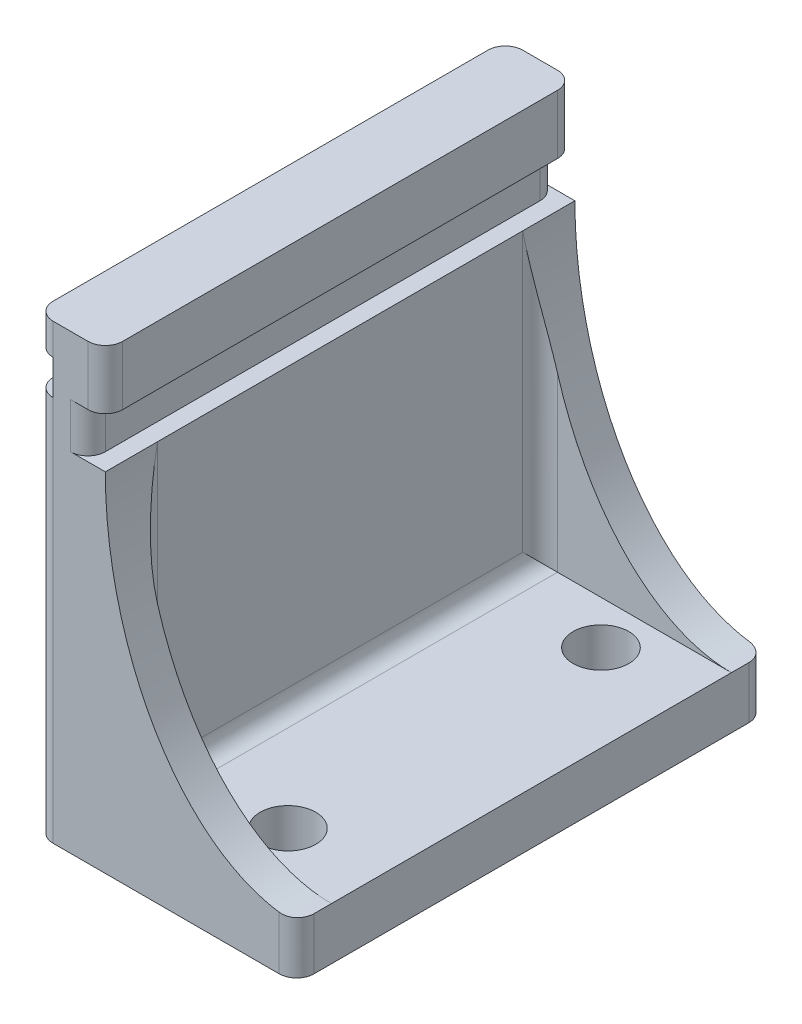
SolidWorks part; units mm, degrees
material "ABS"
ref_plane "Front Plane" through (0, 0, 0) normal (0, 0, 1) x (1, 0, 0)
ref_plane "Top Plane" through (0, 0, 0) normal (0, 1, 0) x (1, 0, 0)
ref_plane "Right Plane" through (0, 0, 0) normal (1, 0, 0) x (0, 0, -1)
sketch "Sketch1" plane through (0, 0, 0) normal (0, 1, 0) x (1, 0, 0)
  line L0 (2.5, 13.5) -> (2.5, -13.5) construction
  line L1 (-7.5, -13.5) -> (7.5, -13.5)
  line L2 (-7.5, -13.5) -> (-7.5, 13.5)
  line L3 (-7.5, 13.5) -> (7.5, 13.5)
  line L4 (7.5, -13.5) -> (7.5, 13.5)
  line L5 (0, 13.5) -> (0, -13.5) construction
  line L6 (-7.5, 0) -> (7.5, 0) construction
  circle A0 centre (2.5, 9) radius 1.6
  circle A2 centre (2.5, -9) radius 1.6
  point P0 (0, 0)
  dimension "D4" = 3.2
  dimension "D5" = 9
  dimension "D1" = 15
  dimension "D2" = 27
  dimension "D3" = 10
extrude "Boss-Extrude1" add sketch "Sketch1" along normal blind 3
sketch "Sketch2" plane through (0, 3, 0) normal (0, 1, 0) x (1, 0, 0)
  line L0 (-3.5, 13.5) -> (-3.5, -13.5)
  line L1 (-7.5, 13.5) -> (7.5, 13.5)
  line L2 (-7.5, 13.5) -> (-7.5, -13.5)
  line L3 (-7.5, -13.5) -> (7.5, -13.5)
  line L4 (7.5, 13.5) -> (7.5, -13.5)
  line M7 (7.5, 13.5) -> (-7.5, 13.5)
  line M8 (-7.5, 13.5) -> (-7.5, -13.5)
  line M9 (-7.5, -13.5) -> (7.5, -13.5)
  dimension "D1" = 4
extrude "Boss-Extrude2" add sketch "Sketch2" along normal blind 23 contours L0 M7 M8 M9
sketch "Sketch3" plane through (-7.5, 0, 0) normal (-1, 0, 0) x (0, 0, 1)
  line L0 (-13.5, 3) -> (13.5, 3) construction
  line L1 (-13.5, 26) -> (13.5, 26)
  line L2 (-13.5, 26) -> (-13.5, 0)
  line L3 (-13.5, 0) -> (13.5, 0)
  line L4 (13.5, 26) -> (13.5, 0)
  line L5 (-13.5, 22.2) -> (13.5, 22.2)
  line L6 (-13.5, 24.2) -> (13.5, 24.2)
  dimension "D1" = 3
  dimension "D2" = 19.2
  dimension "D3" = 2
extrude "Cut-Extrude1" cut sketch "Sketch3" against normal blind 1 contours L6 L2 L5 L4
sketch "Sketch4" plane through (-3.5, 0, 0) normal (1, 0, 0) x (0, 0, -1)
  line L0 (-13.5, 20) -> (13.5, 20)
  line L1 (-13.5, 26) -> (13.5, 26)
  line L2 (-13.5, 26) -> (-13.5, 3)
  line L3 (-13.5, 3) -> (13.5, 3)
  line L4 (13.5, 26) -> (13.5, 3)
  line L5 (-13.5, 22.6) -> (13.5, 22.6)
  line M8 (13.5, 3) -> (13.5, 26)
  dimension "D1" = 17
  dimension "D2" = 2.6
extrude "Cut-Extrude2" cut sketch "Sketch4" against normal blind 1 contours L5 L2 L0 M8
sketch "Sketch5" plane through (0, 3, 0) normal (0, 1, 0) x (1, 0, 0)
  line L0 (-3.5, 11.5) -> (7.5, 11.5)
  line L1 (-3.5, 13.5) -> (7.5, 13.5)
  line L2 (-3.5, 13.5) -> (-3.5, -13.5)
  line L3 (-3.5, -13.5) -> (7.5, -13.5)
  line L4 (7.5, 13.5) -> (7.5, -13.5)
  line L5 (7.5, 0) -> (-3.5, 0) construction
  line L6 (-3.5, -11.5) -> (7.5, -11.5)
  line M7 (7.5, 13.5) -> (-3.5, 13.5)
  line M8 (-3.5, 13.5) -> (-3.5, -13.5)
  line M9 (-3.5, -13.5) -> (7.5, -13.5)
  line M10 (7.5, -13.5) -> (7.5, 13.5)
  dimension "D1" = 2
extrude "Boss-Extrude3" add sketch "Sketch5" along normal blind 17 contours L0 M8 M10 M7 | L6 L2 M9 M10
sketch "Sketch7" plane through (0, 0, -11.5) normal (0, 0, 1) x (1, 0, 0)
  line L1 (-3.5, 20) -> (7.5, 20)
  line L2 (-3.5, 20) -> (-3.5, 3)
  line L3 (-3.5, 3) -> (7.5, 3)
  line L4 (7.5, 20) -> (7.5, 3)
  ellipse E0 centre (7.5, 20) end of major axis (7.5, 37) minor radius 11
  dimension "D1" = 11
  dimension "D2" = 17
extrude "Cut-Extrude3" cut sketch "Sketch7" against normal through all both and the other way through all contours E0
fillet "Fillet2" radius 1 8 edges at (-7.5, 25.1, -13.5) (-3.5, 24.3, 13.5) (-3.5, 24.3, -13.5) (-4.5, 21.3, -13.5) (7.5, 1.5, -13.5) (7.5, 1.5, 13.5) (-4.5, 21.3, 13.5) (-7.5, 25.1, 13.5)
fillet "Fillet3" radius 1 3 edges at (-3.5, 11.5, 11.5) (-3.5, 11.5, -11.5) (-3.5, 3, 0)
